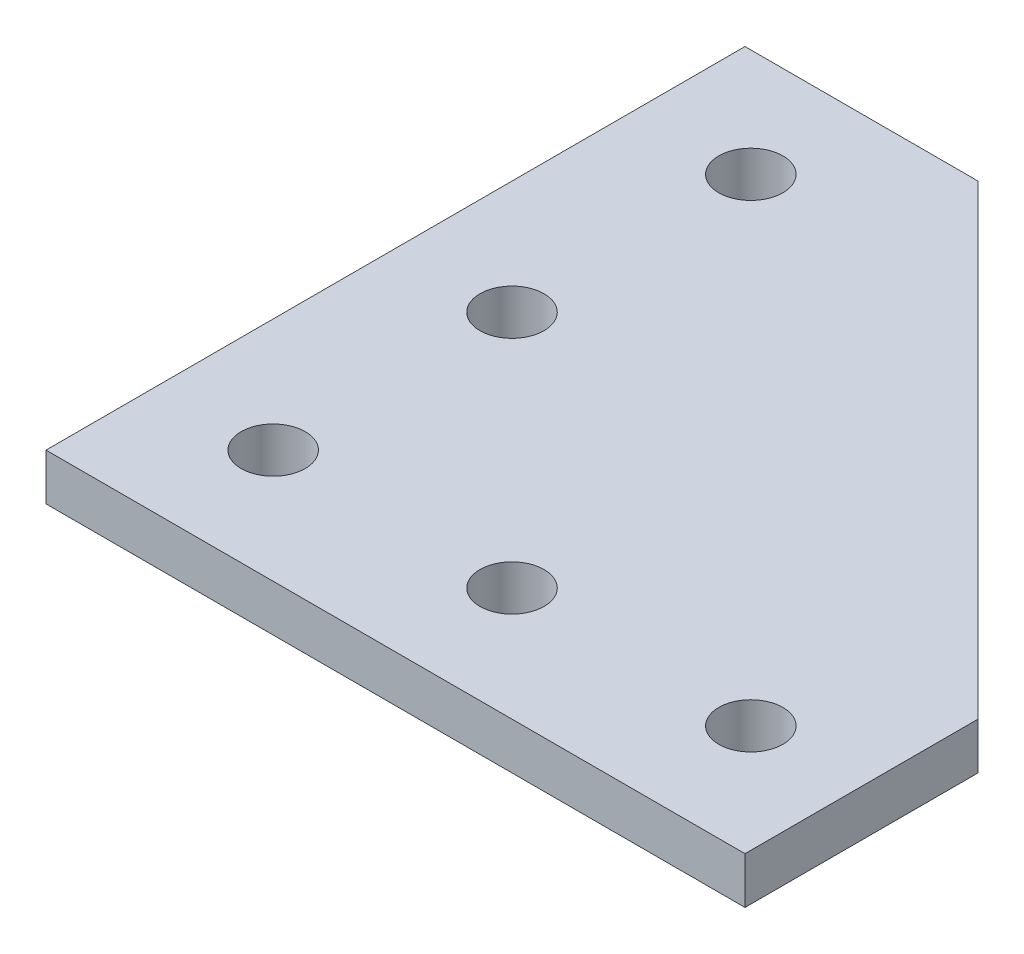
SolidWorks part; units mm, degrees
ref_plane "Front" through (0, 0, 0) normal (0, 0, 1) x (1, 0, 0)
ref_plane "Top" through (0, 0, 0) normal (0, 1, 0) x (1, 0, 0)
ref_plane "Right" through (0, 0, 0) normal (1, 0, 0) x (0, 0, -1)
sketch "Sketch2" plane through (0, 0, 0) normal (0, 1, 0) x (1, 0, 0)
  line L0 (-10, -10) -> (50, -10)
  line L1 (50, -10) -> (50, 10)
  line L2 (50, 10) -> (10, 50)
  line L3 (10, 50) -> (-10, 50)
  line L4 (-10, 50) -> (-10, -10)
  line L5 (0, 50) -> (0, -10) construction
  line L6 (50, 0) -> (-10.2092, 0) construction
  dimension "D1" = 20
  dimension "D2" = 60
extrude "Boss-Extrude1" add sketch "Sketch2" along normal mid plane 4
sketch "Sketch3" plane through (0, 2, 0) normal (0, 1, 0) x (1, 0, 0)
  line L0 (-10, -10) -> (50, -10) construction
  line L3 (-10, 50) -> (-10, -10) construction
  circle A0 centre (-0.25, -0.25) radius 2.75
  dimension "D1" = 5.5
  dimension "D2" = 9.75
  dimension "D3" = 9.75
extrude "Cut-Extrude1" cut sketch "Sketch3" against normal through all both and the other way through all contours A0
pattern_linear "LPattern1" count 3 spacing 20.5 along (0, 0, -1) count 3 spacing 20.5 along (1, 0, 0) skipping (1, 1), (1, 2), (2, 1), (2, 2) of "Cut-Extrude1"
